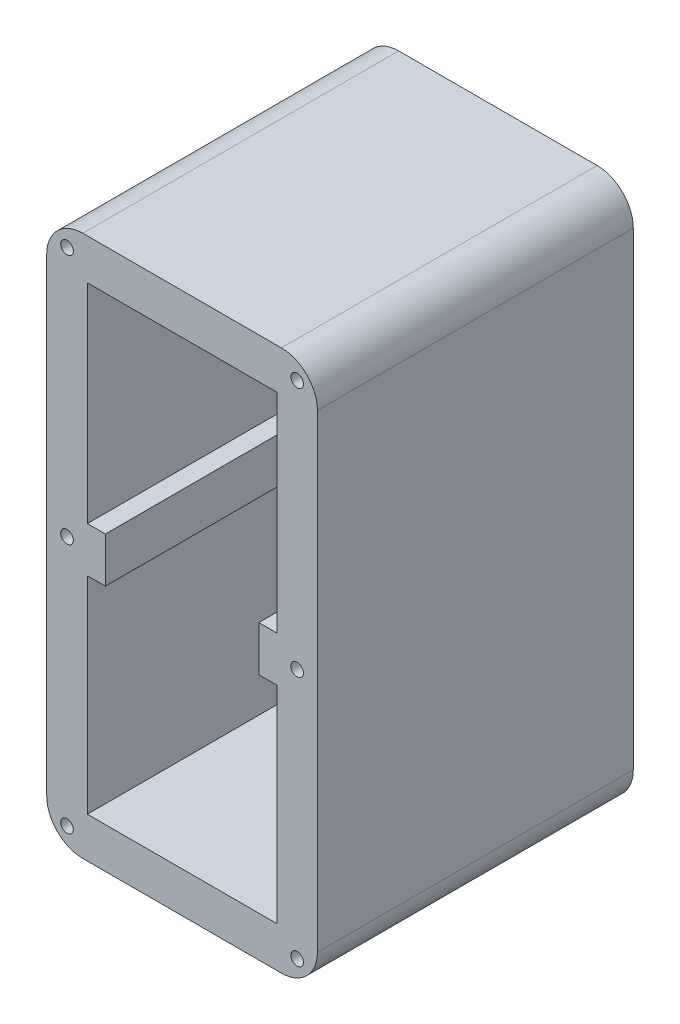
SolidWorks part; units mm, degrees
ref_plane "Front Plane" through (0, 0, 0) normal (0, 0, 1) x (1, 0, 0)
ref_plane "Top Plane" through (0, 0, 0) normal (0, 1, 0) x (1, 0, 0)
ref_plane "Right Plane" through (0, 0, 0) normal (1, 0, 0) x (0, 0, -1)
sketch "Sketch1" plane through (0, 0, 0) normal (0, 0, 1) x (1, 0, 0)
  line L0 (-38, -20.6189) -> (-34, -20.6189)
  line L1 (-47, 34.6067) -> (13, 34.6067)
  line L2 (-47, 34.6067) -> (-47, -85.3933)
  line L3 (-47, -85.3933) -> (13, -85.3933)
  line L4 (13, 34.6067) -> (13, -85.3933)
  line L5 (-38, -76.3933) -> (4, -76.3933)
  line L6 (-38, -76.3933) -> (-38, 25.6067)
  line L7 (-38, 25.6067) -> (4, 25.6067)
  line L8 (4, -76.3933) -> (4, 25.6067)
  line L9 (-38, -30.6189) -> (-34, -30.6189)
  line L10 (-34, -20.6189) -> (-34, -30.6189)
  line L11 (0, -20.6189) -> (0, -30.6189)
  line L12 (0, -30.6189) -> (4, -30.6189)
  line L13 (0, -20.6189) -> (4, -20.6189)
  circle A0 centre (8.5, 30.1067) radius 1.4
  circle A1 centre (-42.5, 30.1067) radius 1.4
  circle A2 centre (-42.5, -80.8933) radius 1.4
  circle A3 centre (8.5, -80.8933) radius 1.4
  circle A4 centre (-42.5, -25.3933) radius 1.4
  circle A5 centre (8.5, -25.3933) radius 1.4
  point P20 (-47, -25.3933)
  point P30 (-38, -25.3933)
  dimension "D7" = 4.5
  dimension "D9" = 111
  dimension "D11" = 4.5
  dimension "D14" = 4.5
  dimension "D19" = 2.8
  dimension "D21" = 2.8
  dimension "D22" = 2.8
  dimension "D23" = 2.8
  dimension "D24" = 2.8
  dimension "D25" = 2.8
  dimension "D1" = 60
  dimension "D2" = 120
  dimension "D3" = 102
  dimension "D4" = 42
  dimension "D5" = 9
  dimension "D6" = 9
  dimension "D8" = 4
  dimension "D10" = 10
  dimension "D12" = 4.5
  dimension "D13" = 4.5
  dimension "D15" = 4.5
  dimension "D16" = 4.5
  dimension "D17" = 55.5
  dimension "D18" = 55.5
  dimension "D20" = 55.5
extrude "Boss-Extrude1" add sketch "Sketch1" against normal blind 70 contours L4 L1 L2 L3 A5 A4 A3 A2 A1 A0 L8 L5 L6 L7 region at (-17, 33.2651, 0)
extrude "Boss-Extrude3" add sketch "Sketch1<5>" against normal blind 60 contours L10 L0 L6 L9 | L13 L11 L12 L8 region at (-36, -25.6189, 0) region at (2, -25.6189, 0)
sketch "Sketch1<5>" plane through (0, 0, 0) normal (0, 0, 1) x (1, 0, 0) same geometry as "Sketch1"
extrude "Boss-Extrude5" add sketch "Sketch1<7>" against normal blind 62 contours A5 | A4 | A3 | A2 | A0 | A1 region at (8.5, -80.8933, 0) region at (-42.5, -25.3933, 0) region at (8.5, -25.3933, 0)
sketch "Sketch1<7>" plane through (0, 0, 0) normal (0, 0, 1) x (1, 0, 0) same geometry as "Sketch1"
extrude "Cut-Extrude1" cut sketch "Sketch1<8>" against normal blind 10 contours A4 | A5 | A0 | A1 | A3 | A2 region at (8.5, 30.1067, 0) region at (-42.5, 30.1067, 0) region at (-42.5, -25.3933, 0) region at (8.5, -25.3933, 0)
sketch "Sketch1<8>" plane through (0, 0, 0) normal (0, 0, 1) x (1, 0, 0) same geometry as "Sketch1"
ref_plane "Plane1" through (-47, 0, 0) normal (-1, 0, 0) x (0, 0, 1)
sketch "Sketch2" plane through (-47, 0, 0) normal (-1, 0, 0) x (0, 0, 1)
fillet "Fillet1" radius 8 4 edges at (13, -85.3933, -35) (-47, -85.3933, -35) (-47, 34.6067, -35) (13, 34.6067, -35)
